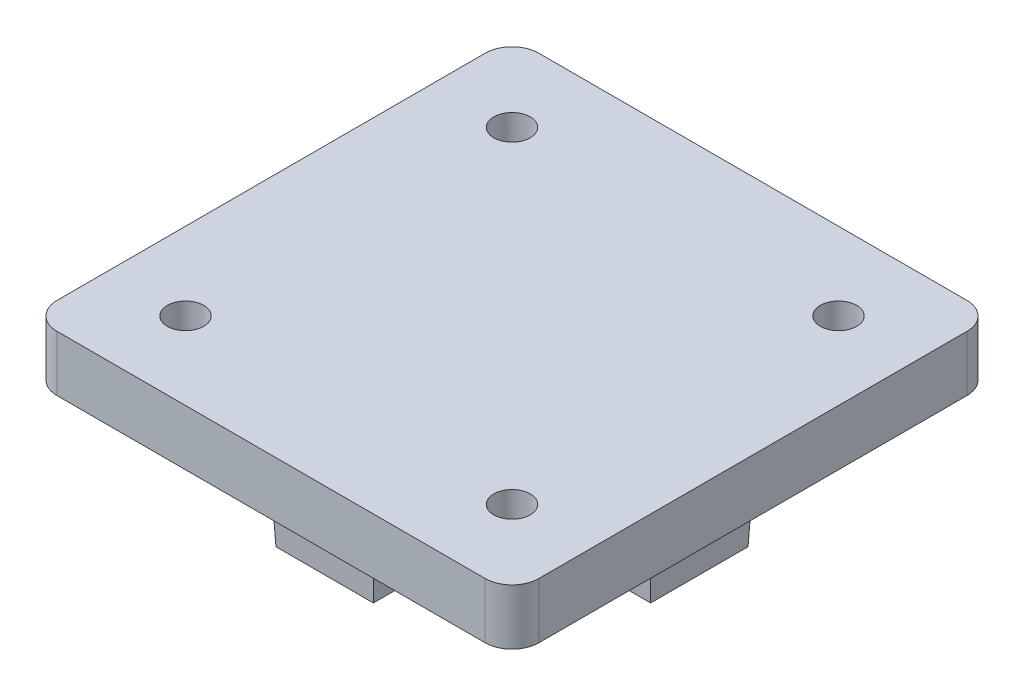
SolidWorks part; units mm, degrees
ref_plane "Front Plane" through (0, 0, 0) normal (0, 0, 1) x (1, 0, 0)
ref_plane "Top Plane" through (0, 0, 0) normal (0, 1, 0) x (1, 0, 0)
ref_plane "Right Plane" through (0, 0, 0) normal (1, 0, 0) x (0, 0, -1)
sketch "Sketch1" plane through (0, 0, 0) normal (0, 1, 0) x (1, 0, 0)
  line L1 (-22.5, 22.5) -> (22.5, 22.5)
  line L2 (-22.5, 22.5) -> (-22.5, -22.5)
  line L3 (-22.5, -22.5) -> (22.5, -22.5)
  line L4 (22.5, 22.5) -> (22.5, -22.5)
  line L5 (-22.5, 22.5) -> (22.5, -22.5) construction
  line L6 (-22.5, -22.5) -> (22.5, 22.5) construction
  point P0 (0, 0)
  dimension "D1" = 45
  dimension "D2" = 45
extrude "Boss-Extrude1" add sketch "Sketch1" against normal blind 5.2
sketch "Sketch2" plane through (0, -5.2, 0) normal (0, -1, 0) x (1, 0, 0)
  line L0 (-4.85, 12) -> (-4.85, 17.8)
  line L1 (-12, -4.85) -> (-17.8, -4.85)
  line L2 (-12, -4.85) -> (-12, 4.85)
  line L3 (-12, 4.85) -> (-17.8, 4.85)
  line L4 (-17.8, -4.85) -> (-17.8, 4.85)
  line L5 (-12, -4.85) -> (-17.8, 4.85) construction
  line L6 (-12, 4.85) -> (-17.8, -4.85) construction
  line L7 (-4.85, 12) -> (4.85, 12)
  line L8 (4.85, 12) -> (4.85, 17.8)
  line L9 (-4.85, 17.8) -> (4.85, 17.8)
  line L10 (-4.85, 12) -> (4.85, 17.8) construction
  line L11 (4.85, 12) -> (-4.85, 17.8) construction
  line L12 (12, 4.85) -> (17.8, 4.85)
  line L13 (12, 4.85) -> (12, -4.85)
  line L14 (12, -4.85) -> (17.8, -4.85)
  line L15 (17.8, 4.85) -> (17.8, -4.85)
  line L16 (12, 4.85) -> (17.8, -4.85) construction
  line L17 (12, -4.85) -> (17.8, 4.85) construction
  line L18 (4.85, -12) -> (4.85, -17.8)
  line L19 (4.85, -12) -> (-4.85, -12)
  line L20 (-4.85, -12) -> (-4.85, -17.8)
  line L21 (4.85, -17.8) -> (-4.85, -17.8)
  line L22 (4.85, -12) -> (-4.85, -17.8) construction
  line L23 (-4.85, -12) -> (4.85, -17.8) construction
  point P0 (-14.9, 0)
  point P5 (0, 14.9)
  point P13 (14.9, 0)
  point P18 (0, -14.9)
  point P23 (0, 0)
  dimension "D1" = 5.8
  dimension "D2" = 9.7
  dimension "D3" = 12
  dimension "D4" = 4
extrude "Boss-Extrude2" add sketch "Sketch2" along normal blind 7
sketch "Sketch3" plane through (0, 0, 0) normal (0, 1, 0) x (1, 0, 0)
  line L1 (-15.25, 15.25) -> (15.25, 15.25) construction
  line L2 (-15.25, 15.25) -> (-15.25, -15.25) construction
  line L3 (-15.25, -15.25) -> (15.25, -15.25) construction
  line L4 (15.25, 15.25) -> (15.25, -15.25) construction
  line L5 (-15.25, 15.25) -> (15.25, -15.25) construction
  line L6 (-15.25, -15.25) -> (15.25, 15.25) construction
  circle A0 centre (-15.25, 15.25) radius 1.7
  circle A1 centre (15.25, 15.25) radius 1.7
  circle A2 centre (-15.25, -15.25) radius 1.7
  circle A3 centre (15.25, -15.25) radius 1.7
  point P0 (0, 0)
  dimension "D3" = 3.4
  dimension "D1" = 30.5
  dimension "D2" = 30.5
extrude "Cut-Extrude1" cut sketch "Sketch3" against normal through all both and the other way through all
sketch "Sketch4" plane through (0, -5.2, 0) normal (0, -1, 0) x (1, 0, 0)
  line L0 (12.6, 13.72) -> (15.25, 12.19)
  line L1 (-13.72, 12.6) -> (-12.19, 15.25)
  line L2 (-12.19, 15.25) -> (-13.72, 17.9)
  line L3 (-13.72, 17.9) -> (-16.78, 17.9)
  line L4 (-16.78, 17.9) -> (-18.31, 15.25)
  line L5 (-18.31, 15.25) -> (-16.78, 12.6)
  line L6 (-16.78, 12.6) -> (-13.72, 12.6)
  line L7 (15.25, 12.19) -> (17.9, 13.72)
  line L8 (17.9, 13.72) -> (17.9, 16.78)
  line L9 (17.9, 16.78) -> (15.25, 18.31)
  line L10 (15.25, 18.31) -> (12.6, 16.78)
  line L11 (12.6, 16.78) -> (12.6, 13.72)
  line L12 (13.72, -12.6) -> (12.19, -15.25)
  line L13 (12.19, -15.25) -> (13.72, -17.9)
  line L14 (13.72, -17.9) -> (16.78, -17.9)
  line L15 (16.78, -17.9) -> (18.31, -15.25)
  line L16 (18.31, -15.25) -> (16.78, -12.6)
  line L17 (16.78, -12.6) -> (13.72, -12.6)
  line L18 (-12.6, -13.72) -> (-15.25, -12.19)
  line L19 (-15.25, -12.19) -> (-17.9, -13.72)
  line L20 (-17.9, -13.72) -> (-17.9, -16.78)
  line L21 (-17.9, -16.78) -> (-15.25, -18.31)
  line L22 (-15.25, -18.31) -> (-12.6, -16.78)
  line L23 (-12.6, -16.78) -> (-12.6, -13.72)
  circle A0 centre (-15.25, 15.25) radius 2.65 construction
  point P30 (0, 0)
  dimension "D1" = 5.3
  dimension "D2" = 4
extrude "Cut-Extrude2" cut sketch "Sketch4" against normal blind 2.5
fillet "Fillet1" radius 2.5 4 edges at (-22.5, -2.6, 22.5) (22.5, -2.6, 22.5) (-22.5, -2.6, -22.5) (22.5, -2.6, -22.5)
chamfer "Chamfer1" distance 7 distance2 0.3 16 edges at (-4.85, -12.2, -14.9) (0, -12.2, -12) (4.85, -12.2, -14.9) (0, -12.2, -17.8) (-14.9, -12.2, 4.85) (-12, -12.2, 0) (-14.9, -12.2, -4.85) (-17.8, -12.2, 0) (4.85, -12.2, 14.9) (0, -12.2, 17.8) (-4.85, -12.2, 14.9) (0, -12.2, 12) (14.9, -12.2, 4.85) (12, -12.2, 0) (17.8, -12.2, 0) (14.9, -12.2, -4.85) first distance on face at (-4.85, -8.7, -14.9) first distance on face at (0, -8.7, -12) first distance on face at (4.85, -8.7, -14.9) first distance on face at (0, -8.7, -17.8) first distance on face at (-14.9, -8.7, 4.85) first distance on face at (-12, -8.7, 0) first distance on face at (-14.9, -8.7, -4.85) first distance on face at (-17.8, -8.7, 0) first distance on face at (4.85, -8.7, 14.9) first distance on face at (0, -8.7, 17.8) first distance on face at (-4.85, -8.7, 14.9) first distance on face at (0, -8.7, 12) first distance on face at (14.9, -8.7, 4.85) first distance on face at (12, -8.7, 0) first distance on face at (17.8, -8.7, 0) first distance on face at (14.9, -8.7, -4.85)
